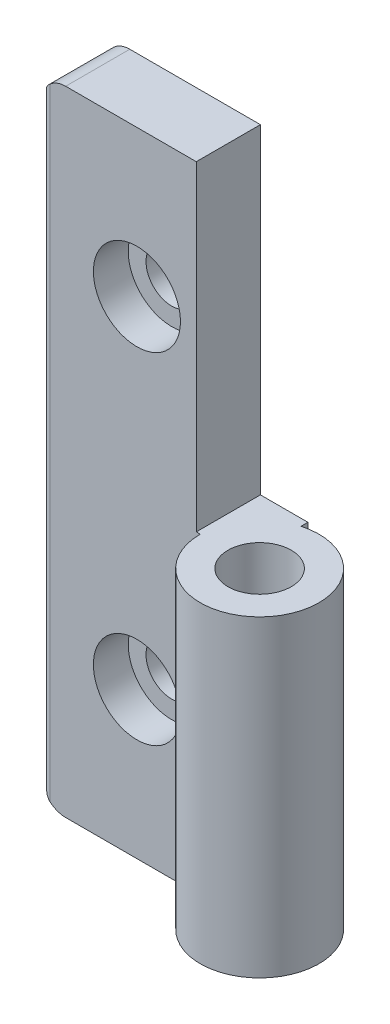
SolidWorks part; units mm, degrees
material "6063-T5"
ref_plane "Piano frontale" through (0, 0, 0) normal (0, 0, 1) x (1, 0, 0)
ref_plane "Piano superiore" through (0, 0, 0) normal (0, 1, 0) x (1, 0, 0)
ref_plane "Piano destro" through (0, 0, 0) normal (1, 0, 0) x (0, 0, -1)
ref_plane "Plane1" through (0, -40, 0) normal (0, -1, 0) x (1, 0, 0)
sketch "Sketch1" plane through (0, -40, 0) normal (0, -1, 0) x (1, 0, 0)
  line L0 (-2, -8.1) -> (-2, -7.2284)
  line L1 (-7.5, 0) -> (-27.5, 0)
  line L2 (-27.5, 0) -> (-27.5, -8.1)
  line L3 (-27.5, -8.1) -> (-2, -8.1)
  arc A0 (-2, -7.2284) -> (-7.5, 0) centre (0, 0) ccw
extrude "Extrude1" add sketch "Sketch1" against normal blind 39.5
sketch "Sketch2" plane through (0, -0.5, 0) normal (0, 1, 0) x (-1, 0, 0)
  line L0 (27.5, -8.1) -> (8, -8.1)
  line L1 (8, -8.1) -> (8, 0)
  line L2 (8, 0) -> (27.5, 0)
  line L3 (27.5, 0) -> (27.5, -8.1)
extrude "Extrude2" add sketch "Sketch2" along normal blind 40.5
hole_wizard "HoleWzd1" positions "Sketch4" profile "Sketch3" hole size "Ø8.0" standard "Ansi Metric"
sketch "Sketch4" plane through (0, -40, 0) normal (0, -1, 0) x (-1, 0, 0)
  point P0 (0, 0)
sketch "Sketch3" plane through (0, -40, 0) normal (1, 0, 0) x (0, 0, -1)
  line L0 (0, 0) -> (0, 80)
  line L1 (0, 80) -> (4, 80)
  line L2 (4, 80) -> (4, 0)
  line L5 (4, 0) -> (0, 0)
  line L11 (0, -6.35) -> (0, 107.95) construction
  dimension "Thru Hole Dia." = 8
  dimension "Thru Hole Depth" = 80
hole_wizard "HoleWzd2" positions "Sketch6" profile "Sketch5" counterbore size "M6" standard "Ansi Metric"
sketch "Sketch6" plane through (0, 0, 0) normal (0, 0, 1) x (1, 0, 0)
  point P0 (-15.5, -21.5)
  point P1 (-15.5, 21.5)
sketch "Sketch5" plane through (-15.5, -21.5, 0) normal (1, 0, 0) x (0, -1, 0)
  line L0 (0, 0) -> (0, 8.1)
  line L1 (0, 8.1) -> (3.25, 8.1)
  line L3 (3.25, 8.1) -> (3.25, 4.4)
  line L4 (3.25, 4.4) -> (5.5, 4.4)
  line L5 (5.5, 4.4) -> (5.5, 0)
  line L7 (5.5, 0) -> (0, 0)
  line L11 (0, -6.35) -> (0, 107.95) construction
  dimension "Thru Hole Dia." = 6.5
  dimension "Thru Hole Depth" = 8.1
  dimension "C'Bore Dia." = 11
  dimension "C'Bore Depth" = 4.4
fillet "Fillet1" radius 1 1 edges at (-27.5, 0, 0) tangent propagation no
fillet "Fillet2" radius 3 2 edges at (-27.5, -40, -4.55) (-27.5, 40, -4.55) tangent propagation no
